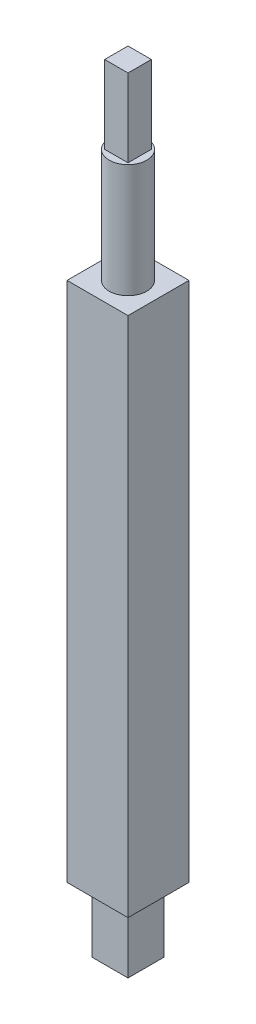
SolidWorks part; units mm, degrees
ref_plane "Front Plane" through (0, 0, 0) normal (0, 0, 1) x (1, 0, 0)
ref_plane "Top Plane" through (0, 0, 0) normal (0, 1, 0) x (1, 0, 0)
ref_plane "Right Plane" through (0, 0, 0) normal (1, 0, 0) x (0, 0, -1)
sketch "Sketch1" plane through (0, 0, 0) normal (0, 1, 0) x (1, 0, 0)
  line L1 (-5.969, 5.969) -> (5.969, 5.969)
  line L2 (-5.969, 5.969) -> (-5.969, -5.969)
  line L3 (-5.969, -5.969) -> (5.969, -5.969)
  line L4 (5.969, 5.969) -> (5.969, -5.969)
  line L9 (-5.969, 5.969) -> (5.969, -5.969) construction
  line L10 (-5.969, -5.969) -> (5.969, 5.969) construction
  point P0 (0, 0)
  dimension "D1" = 11.938
  dimension "D2" = 11.938
extrude "Boss-Extrude1" add sketch "Sketch1" along normal blind 213.106
sketch "Sketch2" plane through (0, 213.106, 0) normal (0, 1, 0) x (1, 0, 0)
  circle A0 centre (0, 0) radius 3.6805
  dimension "D1" = 7.3609
extrude "Boss-Extrude2" add sketch "Sketch2" along normal blind 22.225
sketch "Sketch3" plane through (0, 0, 0) normal (0, -1, 0) x (-1, 0, 0)
  circle A0 centre (0, 0) radius 3.6805
  dimension "D1" = 7.3609
extrude "Boss-Extrude3" add sketch "Sketch3" along normal blind 28.575
sketch "Sketch4" plane through (0, 235.331, 0) normal (0, 1, 0) x (1, 0, 0)
  line L1 (-2.286, 2.286) -> (2.286, 2.286)
  line L2 (-2.286, 2.286) -> (-2.286, -2.286)
  line L3 (-2.286, -2.286) -> (2.286, -2.286)
  line L4 (2.286, 2.286) -> (2.286, -2.286)
  line L5 (-2.286, 2.286) -> (2.286, -2.286) construction
  line L6 (-2.286, -2.286) -> (2.286, 2.286) construction
  point P0 (0, 0)
  dimension "D1" = 4.572
  dimension "D2" = 4.572
extrude "Boss-Extrude4" add sketch "Sketch4" along normal blind 15.24
sketch "Sketch5" plane through (0, -28.575, 0) normal (0, -1, 0) x (-1, 0, 0)
  circle A0 centre (0, 0) radius 9.1375
extrude "Cut-Extrude1" cut sketch "Sketch5" against normal blind 139.573
sketch "Sketch6" plane through (0, 110.998, 0) normal (0, -1, 0) x (-1, 0, 0)
  line L1 (3.5052, 3.5052) -> (-3.5052, 3.5052)
  line L2 (3.5052, 3.5052) -> (3.5052, -3.5052)
  line L3 (3.5052, -3.5052) -> (-3.5052, -3.5052)
  line L4 (-3.5052, 3.5052) -> (-3.5052, -3.5052)
  line L5 (3.5052, 3.5052) -> (-3.5052, -3.5052) construction
  line L6 (3.5052, -3.5052) -> (-3.5052, 3.5052) construction
  point P0 (0, 0)
  dimension "D1" = 7.0104
  dimension "D2" = 7.0104
extrude "Boss-Extrude5" add sketch "Sketch6" along normal blind 12.7
